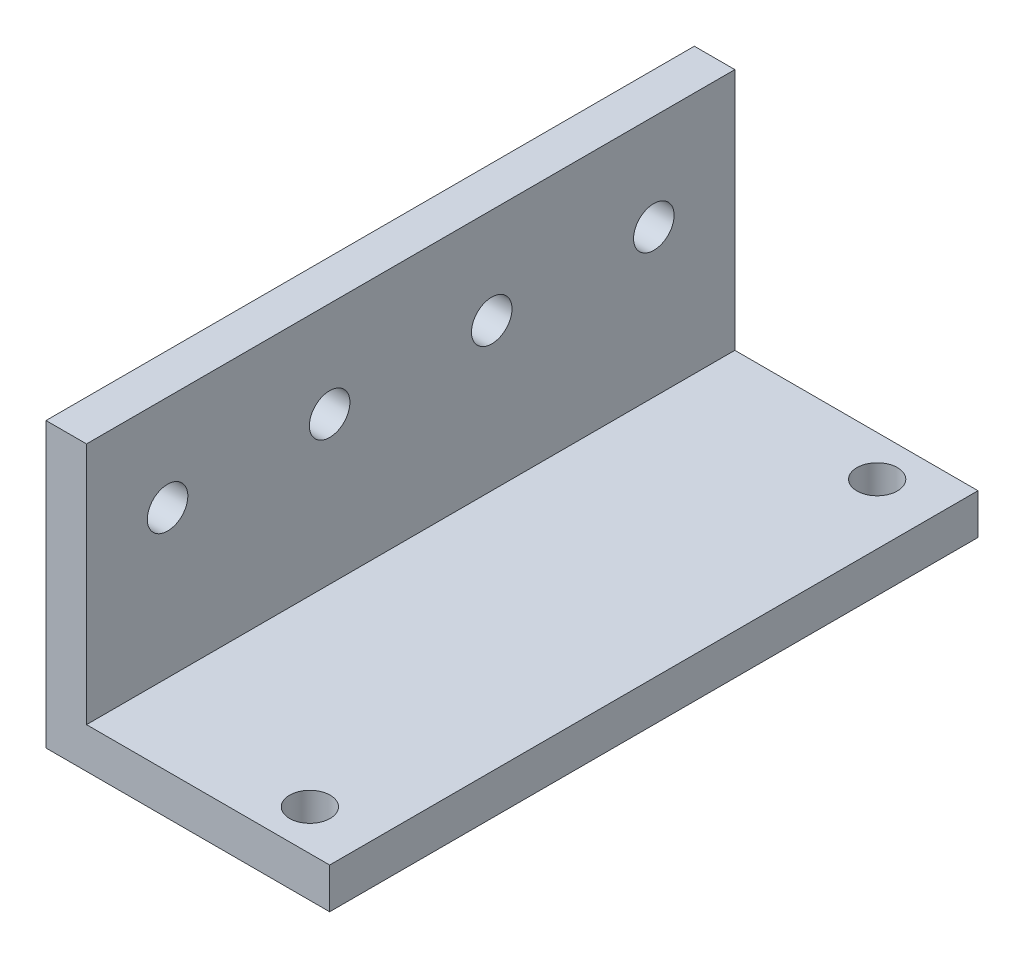
SolidWorks part; units mm, degrees
ref_plane "Front Plane" through (0, 0, 0) normal (0, 0, 1) x (1, 0, 0)
ref_plane "Top Plane" through (0, 0, 0) normal (0, 1, 0) x (1, 0, 0)
ref_plane "Right Plane" through (0, 0, 0) normal (1, 0, 0) x (0, 0, -1)
sketch "Sketch1" plane through (0, 0, 0) normal (0, 0, 1) x (1, 0, 0)
  line L1 (0, 0) -> (44.45, 0)
  line L2 (0, 0) -> (0, 44.45)
  line L3 (0, 44.45) -> (44.45, 44.45)
  line L4 (44.45, 0) -> (44.45, 44.45)
  line L5 (44.45, 44.45) -> (6.35, 44.45)
  line L6 (44.45, 44.45) -> (44.45, 6.35)
  line L7 (44.45, 6.35) -> (6.35, 6.35)
  line L8 (6.35, 44.45) -> (6.35, 6.35)
  dimension "D1" = 6.35
  dimension "D2" = 6.35
  dimension "D3" = 44.45
  dimension "D4" = 44.45
extrude "Boss-Extrude1" add sketch "Sketch1" along normal blind 101.6 contours L8 L3 L2 L1 L4 L7 region at (0.6286, 22.225, 0)
sketch "Sketch2" plane through (0, 6.35, 0) normal (0, 1, 0) x (1, 0, 0)
  line L2 (0, 0) -> (44.45, 0) construction
  line L3 (0, -101.6) -> (44.45, -101.6) construction
  circle A0 centre (35, -95.25) radius 3.175
  circle A1 centre (35, -6.35) radius 3.175
  circle A3 centre (35, 61.5076) radius 3.175 construction
  dimension "D1" = 6.35
  dimension "D3" = 0
  dimension "D4" = 6.35
extrude "Cut-Extrude1" cut sketch "Sketch2" against normal blind 25.146
sketch "Sketch3" plane through (6.35, 0, 0) normal (1, 0, 0) x (0, 0, -1)
  line L0 (-101.6, 44.45) -> (0, 44.45) construction
  line L1 (0, 44.45) -> (0, 6.35) construction
  circle A0 centre (-12.7, 29.45) radius 3.175
  circle A1 centre (-63.5, 29.45) radius 3.175
  circle A2 centre (-88.9, 29.45) radius 3.175
  circle A3 centre (-38.1, 29.45) radius 3.175
  dimension "D1" = 15
  dimension "D2" = 15
  dimension "D3" = 15
  dimension "D4" = 15
  dimension "D5" = 12.7
  dimension "D6" = 88.9
  dimension "D7" = 38.1
  dimension "D8" = 63.5
extrude "Cut-Extrude2" cut sketch "Sketch3" against normal blind 25.146
